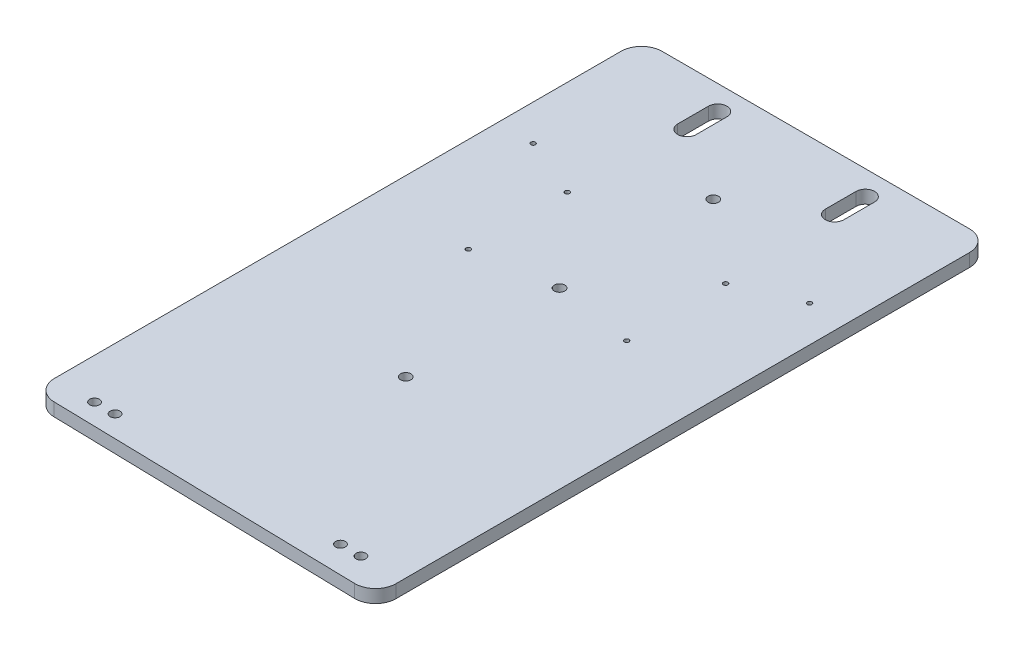
SolidWorks part; units mm, degrees
ref_plane "Front Plane" through (0, 0, 0) normal (0, 0, 1) x (1, 0, 0)
ref_plane "Top Plane" through (0, 0, 0) normal (0, 1, 0) x (1, 0, 0)
ref_plane "Right Plane" through (0, 0, 0) normal (1, 0, 0) x (0, 0, -1)
sketch "Sketch1" plane through (0, 0, 0) normal (0, 1, 0) x (1, 0, 0)
  line L0 (13.6374, 0) -> (183.6374, 0)
  line L1 (183.6374, 0) -> (183.6374, -300)
  line L2 (183.6374, -300) -> (13.6374, -296.1154)
  line L3 (13.6374, -296.1154) -> (13.6374, 0)
  dimension "D1" = 300
  dimension "D2" = 170
extrude "plate" add sketch "Sketch1" along normal blind 6.35
fillet "Fillet1" radius 10 4 edges at (183.6374, 3.175, 300) (13.6374, 3.175, 296.1154) (13.6374, 3.175, 0) (183.6374, 3.175, 0)
hole_wizard "tripod socket Tap Drill for 1/4-20" positions "Sketch4" profile "Sketch5" hole size "1/4-20" standard "ANSI Inch" end condition through all
sketch "Sketch4" plane through (0, 0, 0) normal (0, -1, 0) x (-1, 0, 0)
  line L0 (-98.6374, -15.0951) -> (-98.6374, -298.0577) construction
  line L1 (-23.409, -296.3386) -> (-173.409, -299.7663) construction
  line L3 (-173.6374, 0) -> (-23.6374, 0) construction
  point P0 (-98.6374, -50)
  point P2 (-98.6374, -125)
  point P17 (-98.6374, -200)
  dimension "D1" = 50
  dimension "D2" = 75
  dimension "D3" = 75
sketch "Sketch5" plane through (98.6374, 0, 50) normal (1, 0, 0) x (0, 0, -1)
  line L0 (0, 0) -> (0, 6.35)
  line L1 (0, 6.35) -> (2.5527, 6.35)
  line L2 (2.5527, 6.35) -> (2.5527, 0)
  line L5 (2.5527, 0) -> (0, 0)
  line L11 (0, -6.35) -> (0, 107.95) construction
  dimension "Thru Hole Dia." = 5.1054
  dimension "Thru Hole Depth" = 6.35
sketch "Sketch6" plane through (0, 6.35, 0) normal (0, 1, 0) x (1, 0, 0)
  line L0 (130.1374, -26.8451) -> (130.1374, -11.8451)
  line L1 (139.1374, -26.8451) -> (139.1374, -11.8451)
  line L3 (98.6374, 0) -> (98.6374, -65.5536) construction
  line L4 (173.6374, 0) -> (23.6374, 0) construction
  line L5 (58.1374, -26.8451) -> (58.1374, -11.8451)
  line L6 (67.1374, -26.8451) -> (67.1374, -11.8451)
  circle A1 centre (134.6374, -26.8451) radius 4.5 construction
  arc A2 (139.1374, -11.8451) -> (130.1374, -11.8451) centre (134.6374, -11.8451) ccw
  arc A3 (130.1374, -26.8451) -> (139.1374, -26.8451) centre (134.6374, -26.8451) ccw
  circle A4 centre (62.6374, -26.8451) radius 4.5 construction
  arc A5 (67.1374, -26.8451) -> (58.1374, -26.8451) centre (62.6374, -26.8451) cw
  arc A6 (58.1374, -11.8451) -> (67.1374, -11.8451) centre (62.6374, -11.8451) cw
  dimension "D1" = 9
  dimension "D2" = 15
extrude "camera mount screw clearance" cut sketch "Sketch6" against normal through all
hole_wizard "alignment Tap Drill for M2.5" positions "Sketch7" profile "Sketch8" hole size "M2.5" standard "DIN" end condition through all
sketch "Sketch7" plane through (0, 6.35, 0) normal (0, 1, 0) x (1, 0, 0)
  point P0 (60.0274, -82.5951)
  point P3 (137.2474, -82.5951)
  point P6 (137.2474, -130.8551)
  point P9 (60.0274, -130.8551)
sketch "Sketch8" plane through (60.0274, 6.35, 82.5951) normal (1, 0, 0) x (0, 0, 1)
  line L0 (0, 0) -> (0, 6.35)
  line L1 (0, 6.35) -> (1.1176, 6.35)
  line L2 (1.1176, 6.35) -> (1.1176, 0)
  line L5 (1.1176, 0) -> (0, 0)
  line L11 (0, -6.35) -> (0, 107.95) construction
  dimension "Thru Hole Dia." = 2.2352
  dimension "Thru Hole Depth" = 6.35
hole_wizard "clamp Tap Drill for M2.5" positions "Sketch9" profile "Sketch10" hole size "M2.5" standard "DIN" end condition through all
sketch "Sketch9" plane through (0, 6.35, 0) normal (0, 1, 0) x (1, 0, 0)
  line L2 (98.6374, 0) -> (98.409, -298.0525) construction
  line L3 (173.6374, 0) -> (23.6374, 0) construction
  line L4 (23.409, -296.3386) -> (173.409, -299.7663) construction
  line L7 (29.1374, -70.35) -> (44.1374, -70.35) construction
  point P0 (31.1374, -70.35)
  point P17 (166.0295, -70.4534)
  dimension "D1" = 2
sketch "Sketch10" plane through (31.1374, 6.35, 70.35) normal (1, 0, 0) x (0, 0, 1)
  line L0 (0, 0) -> (0, 6.35)
  line L1 (0, 6.35) -> (1.1176, 6.35)
  line L2 (1.1176, 6.35) -> (1.1176, 0)
  line L5 (1.1176, 0) -> (0, 0)
  line L11 (0, -6.35) -> (0, 107.95) construction
  dimension "Thru Hole Dia." = 2.2352
  dimension "Thru Hole Depth" = 6.35
sketch "Sketch11" plane through (0, 6.35, 0) normal (0, 1, 0) x (1, 0, 0)
  line L0 (23.409, -296.3386) -> (173.409, -299.7663) construction
  line L1 (33.409, -286.5645) -> (43.409, -286.5645) construction
  line L2 (98.409, -298.0525) -> (98.6374, 0) construction
  line L3 (173.6374, 0) -> (23.6374, 0) construction
  line L4 (163.4265, -286.6642) -> (153.4265, -286.6489) construction
  circle A0 centre (33.409, -286.5645) radius 2.3813
  circle A1 centre (43.409, -286.5645) radius 2.3813
  circle A2 centre (153.4265, -286.6489) radius 2.3813
  circle A3 centre (163.4265, -286.6642) radius 2.3813
  dimension "D1" = 4.7625
  dimension "D2" = 10
  dimension "D3" = 10
  dimension "D4" = 10
extrude "cable ties holes" cut sketch "Sketch11" against normal through all
